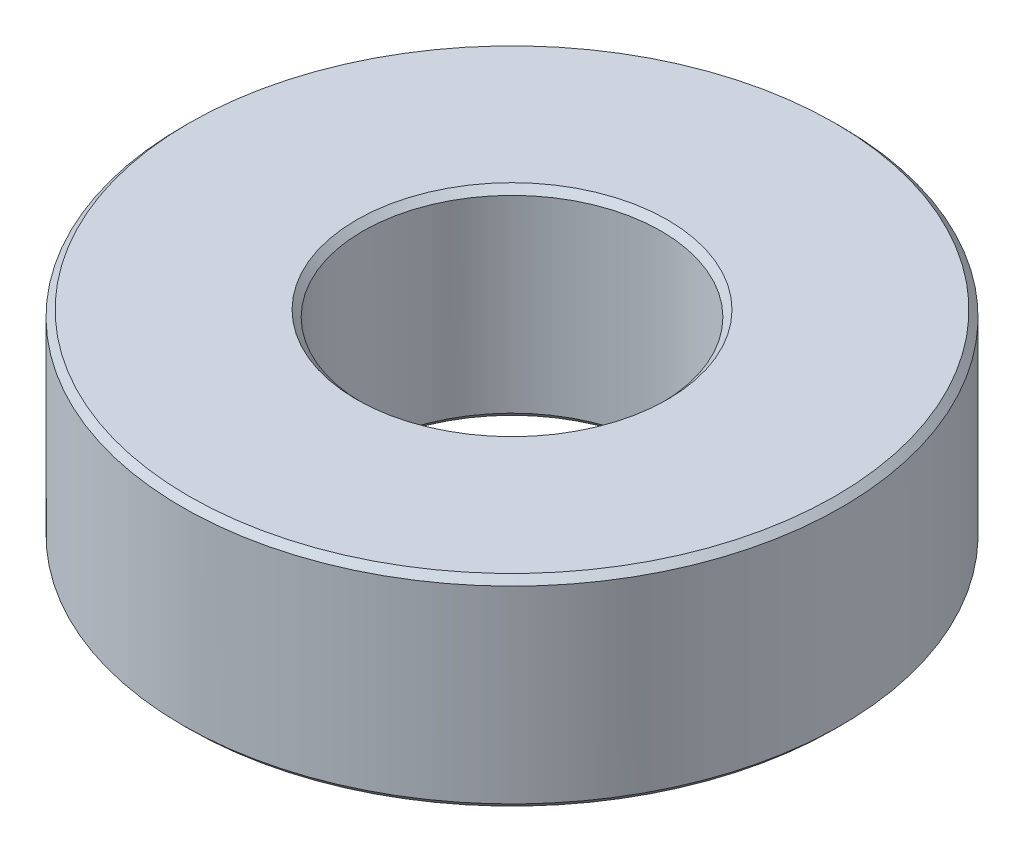
SolidWorks part; units mm, degrees
ref_plane "Front Plane" through (0, 0, 0) normal (0, 0, 1) x (1, 0, 0)
ref_plane "Top Plane" through (0, 0, 0) normal (0, 1, 0) x (1, 0, 0)
ref_plane "Right Plane" through (0, 0, 0) normal (1, 0, 0) x (0, 0, -1)
sketch "Sketch1" plane through (0, 0, 0) normal (0, 1, 0) x (1, 0, 0)
  circle A0 centre (0, 0) radius 22.5
  dimension "SLEEVE_OD" = 45
extrude "Boss-Extrude1" add sketch "Sketch1" along normal blind 13.7567
sketch "Sketch2" plane through (0, 0, 0) normal (0, 1, 0) x (1, 0, 0)
  circle A0 centre (0, 0) radius 10.1813
  dimension "BORE_D" = 20.3627
extrude "Cut-Extrude1" cut sketch "Sketch2" along normal through all
chamfer "Chamfer1" distance 0.4395 angle 45 4 edges at (0, 13.7567, 10.1813) (0, 0, 10.1813) (0, 0, 22.5) (0, 13.7567, 22.5)
